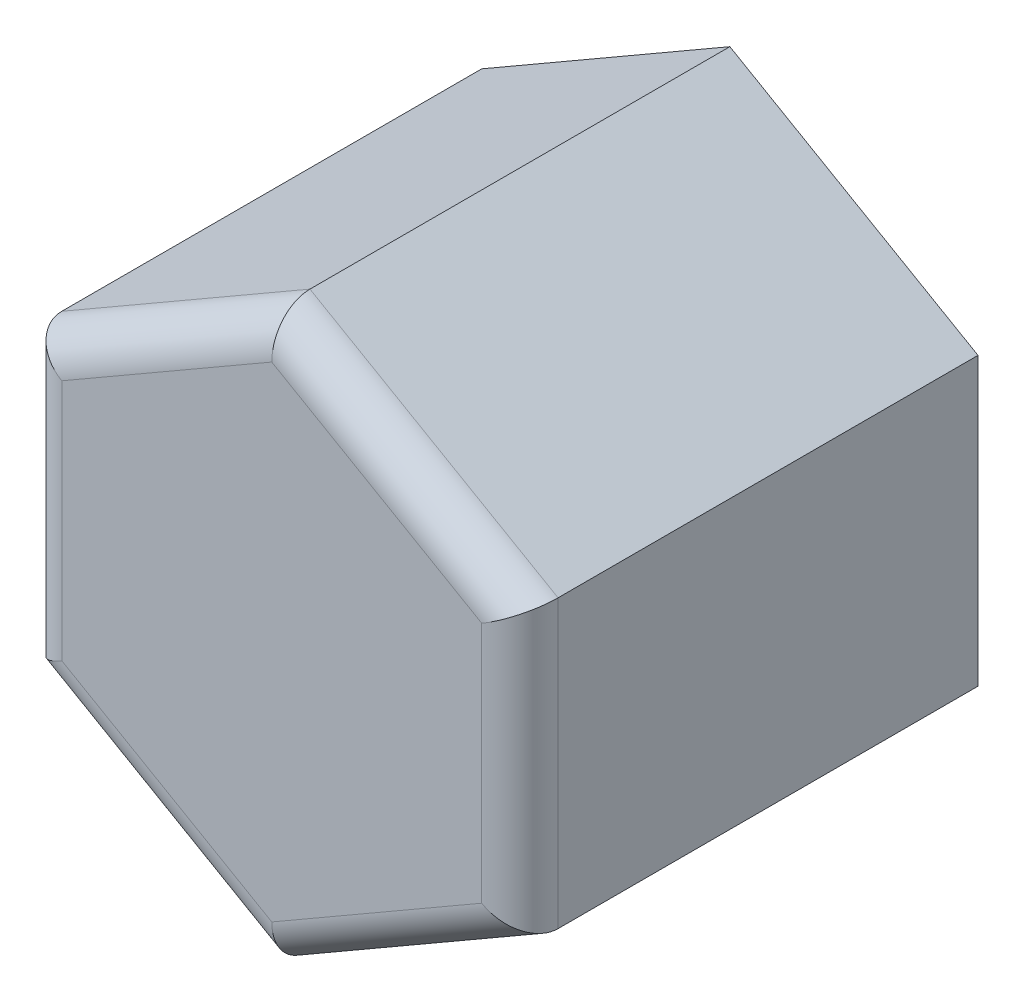
SolidWorks part; units mm, degrees
material "1.0070 (E360)"
ref_plane "Спереди" through (0, 0, 0) normal (0, 0, 1) x (1, 0, 0)
ref_plane "Сверху" through (0, 0, 0) normal (0, 1, 0) x (1, 0, 0)
ref_plane "Справа" through (0, 0, 0) normal (1, 0, 0) x (0, 0, -1)
sketch "Эскиз1" plane through (0, 0, 0) normal (0, 0, 1) x (1, 0, 0)
  line L1 (0, 7.5056) -> (-6.5, 3.7528)
  line L2 (-6.5, 3.7528) -> (-6.5, -3.7528)
  line L3 (-6.5, -3.7528) -> (0, -7.5056)
  line L4 (0, -7.5056) -> (6.5, -3.7528)
  line L5 (6.5, -3.7528) -> (6.5, 3.7528)
  line L6 (6.5, 3.7528) -> (0, 7.5056)
  circle A0 centre (0, 0) radius 6.5 construction
  dimension "D1" = 13
extrude "Основа" add sketch "Эскиз1" along normal mid plane 12
sketch "Эскиз3" plane through (0, 0, -6) normal (0, 0, -1) x (-1, 0, 0)
  circle A0 centre (0, 0) radius 4
  dimension "D1" = 8
extrude "Под резьбу" cut sketch "Эскиз3" against normal blind 9.7
thread "Резьба2" pitch 1.25 method extrude profile "Профиль резьбы2" start angle 0, offset 0, length 0, pitch 1.25, diameter 8
ref_plane "Плоскость2" through (4, 0, -6) normal (0, 1, 0) x (-1, 0, 0)
sketch "Профиль резьбы2" plane through (4, 0, -6) normal (0, 1, 0) x (-1, 0, 0)
  line L0 (0, 0) -> (0, 1.25) construction
  line L1 (0, 0) -> (0.6766, 0.3906)
  line L2 (0.6766, 0.3906) -> (0.6766, 0.5469)
  line L3 (0.6766, 0.5469) -> (0, 0.9375)
  line L4 (0.6766, 0.4687) -> (0, 0.4687) construction
  line L11 (0, 0) -> (0, 0.9375)
  point P2 (0, 0)
  dimension "Pitch" = 1.25
  dimension "Profile_Angle" = 60
  dimension "Profile_Land" = 0.1562
  dimension "Profile_Height" = 0.6766
fillet "Скругление1" radius 1 6 edges at (6.5, 0, 6) (3.25, -5.6292, 6) (-3.25, -5.6292, 6) (-6.5, 0, 6) (-3.25, 5.6292, 6) (3.25, 5.6292, 6)
